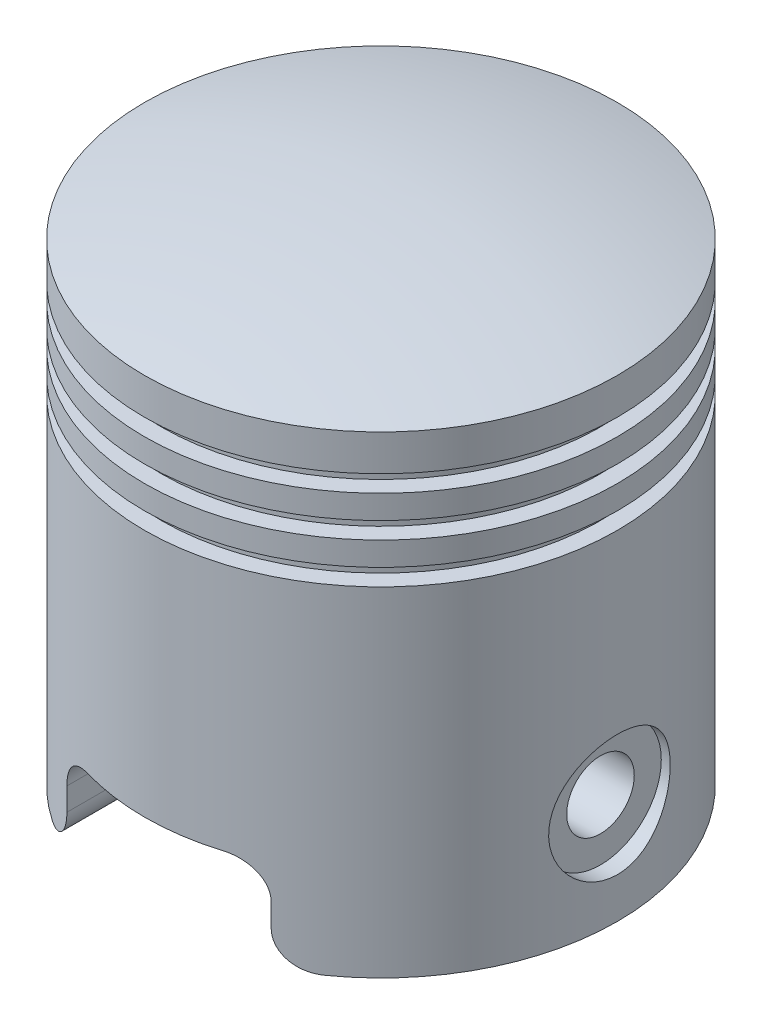
SolidWorks part; units mm, degrees
ref_plane "Front Plane" through (0, 0, 0) normal (0, 0, 1) x (1, 0, 0)
ref_plane "Top Plane" through (0, 0, 0) normal (0, 1, 0) x (1, 0, 0)
ref_plane "Right Plane" through (0, 0, 0) normal (1, 0, 0) x (0, 0, -1)
sketch "Sketch2" plane through (0, 0, 0) normal (0, 0, 1) x (1, 0, 0)
  line L0 (0, 0) -> (35, 0)
  line L1 (35, 0) -> (35, -70)
  line L2 (35, -70) -> (23, -70)
  line L3 (23, -70) -> (23, -10)
  line L4 (0, 0) -> (0, -10)
  line L5 (0, -10) -> (23, -10)
revolve "Revolve1" add sketch "Sketch2" angle 360 about L4 region at (25.2383, -28.5514, 0)
sketch "Sketch3" plane through (0, 0, 0) normal (0, 0, 1) x (1, 0, 0)
  line L0 (0, 0) -> (0, -70)
  line L1 (35, -70) -> (35, 0) construction
  line L2 (35, -5.3607) -> (35, -7.8607)
  line L3 (35, -7.8607) -> (32.5, -7.8607)
  line L4 (32.5, -7.8607) -> (32.5, -5.3607)
  line L5 (32.5, -5.3607) -> (35, -5.3607)
  line L6 (-35, -70) -> (35, -70) construction
revolve "Cut-Revolve2" cut sketch "Sketch3" angle 360 about L0
pattern_linear "LPattern2" count 3 spacing 6 along (0, -1, 0) of "Cut-Revolve2"
sketch "Sketch6" plane through (0, 0, 0) normal (0, 0, 1) x (1, 0, 0)
  line L0 (-35, -70) -> (35, -70) construction
  line L1 (-14.7433, -56.6258) -> (15.2567, -56.6258)
  line L2 (-14.7433, -56.6258) -> (-14.7433, -70)
  line L3 (-14.7433, -70) -> (15.2567, -70)
  line L4 (15.2567, -56.6258) -> (15.2567, -70)
  point P0 (0.2567, -63.3129)
extrude "Cut-Extrude1" cut sketch "Sketch6" against normal mid plane 70 contours L2 L1 L4 L3
fillet "Fillet1" radius 5 1 edges at (-14.7433, -56.6258, 24.6982)
fillet "Fillet2" radius 5 3 edges at (-14.7433, -56.6258, -24.6982) (15.2567, -56.6258, -24.3556) (15.2567, -56.6258, 24.3556)
fillet "Fillet3" radius 5 4 edges at (15.2567, -70, -24.3556) (-14.7433, -70, -24.6982) (15.2567, -70, 24.3556) (-14.7433, -70, 24.6982)
dome "Dome1" faces to dome 1 distance 5 reverse direction no elliptical dome no face at (0, 0, 35) parameters "D1"=5
sketch "Sketch7" plane through (0, 0, 0) normal (1, 0, 0) x (0, 0, -1)
  line L0 (-28.5424, -70) -> (28.5424, -70) construction
  circle A0 centre (0, -55) radius 5
  circle A1 centre (0, -55) radius 7.5
  circle A2 centre (0, -55) radius 9
  dimension "D1" = 15
  dimension "D3" = 10
  dimension "D2" = 15
ref_plane "Plane1" through (35, 0, 0) normal (1, 0, 0) x (0, 0, -1)
sketch "Sketch8" plane through (35, 0, 0) normal (1, 0, 0) x (0, 0, -1)
  line L0 (0, -70) -> (0, -55)
  line L1 (-28.5424, -70) -> (28.5424, -70) construction
  circle A0 centre (0, -55) radius 9
extrude "Cut-Extrude2" cut sketch "Sketch8" against normal blind 2.5 contours A0 region at (35, -61.184, -6.184)
mirror "Mirror1" about plane through (0, 0, 0) normal (1, 0, 0) of "Cut-Extrude2"
sketch "Sketch9" plane through (0, 0, 0) normal (1, 0, 0) x (0, 0, -1)
  circle A2 centre (0, -55) radius 7.5
extrude "Boss-Extrude1" add sketch "Sketch9" along normal mid plane 65
sketch "Sketch10" plane through (0, 0, 0) normal (1, 0, 0) x (0, 0, -1)
  circle A0 centre (0, -55) radius 5
extrude "Cut-Extrude3" cut sketch "Sketch10" against normal mid plane 65
